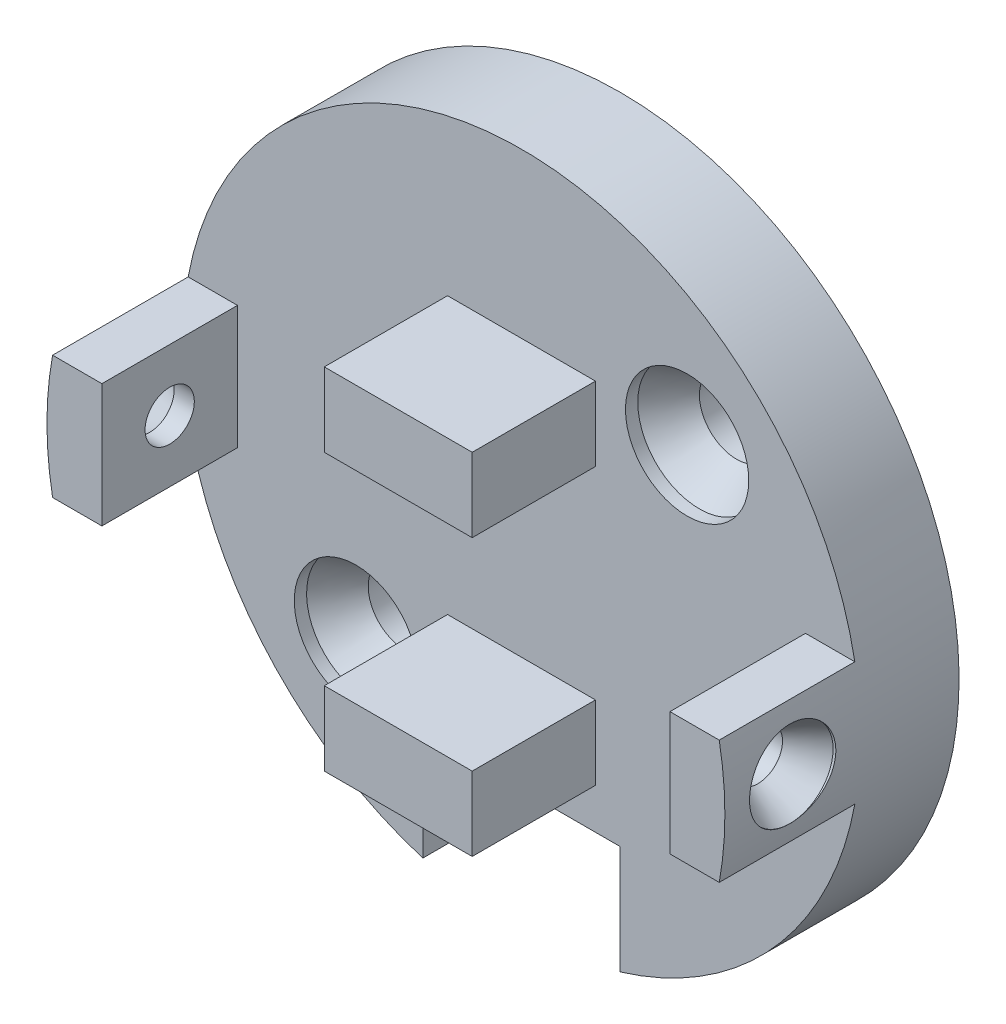
SolidWorks part; units mm, degrees
ref_plane "Front Plane" through (0, 0, 0) normal (0, 0, 1) x (1, 0, 0)
ref_plane "Top Plane" through (0, 0, 0) normal (0, 1, 0) x (1, 0, 0)
ref_plane "Right Plane" through (0, 0, 0) normal (1, 0, 0) x (0, 0, -1)
sketch "Sketch1" plane through (0, 0, 0) normal (0, 0, 1) x (1, 0, 0)
  circle A0 centre (0, 0) radius 13.75
  dimension "D1" = 27.5
extrude "Boss-Extrude1" add sketch "Sketch1" along normal blind 4
sketch "Sketch2" plane through (0, 0, 4) normal (0, 0, 1) x (1, 0, 0)
  line L0 (0, 0) -> (0, 13.75) construction
  line L1 (-13.75, 0) -> (13.75, 0) construction
  line L2 (-13.5208, 2.5) -> (-11.5208, 2.5)
  line L3 (-11.5208, 2.5) -> (-11.5208, -2.5)
  line L4 (-11.5208, -2.5) -> (-13.5208, -2.5)
  line L8 (13.5208, -2.5) -> (11.5208, -2.5)
  line L9 (11.5208, -2.5) -> (11.5208, 2.5)
  line L10 (11.5208, 2.5) -> (13.5208, 2.5)
  line L11 (2.5, 13.5208) -> (2.5, 11.5208) [skipped]
  line L12 (2.5, 11.5208) -> (-2.5, 11.5208) [skipped]
  line L13 (-2.5, 11.5208) -> (-2.5, 13.5208) [skipped]
  circle A0 centre (0, 0) radius 13.75 construction
  circle A1 centre (0, 0) radius 13.75
  point P11 (-11.5208, 0)
  point P14 (11.5208, 0)
  point P21 (0, 0)
  circle M12 centre (0, 0) radius 13.75
  dimension "D1" = 0
  dimension "D2" = 5
  dimension "D3" = 2
  dimension "D5" = 2
  dimension "D6" = 5
  dimension "D4" = 3
extrude "Boss-Extrude2" add sketch "Sketch2" along normal blind 5.5 contours L4 L3 L2 M12 | L10 L9 L8 M12 region at (-12.5984, 0, 4) region at (12.5984, 0, 4)
ref_plane "Plane1" through (0, 0, 6.75) normal (0, 0, 1) x (1, 0, 0)
sketch "Sketch6" plane through (0, 0, 6.75) normal (0, 0, 1) x (1, 0, 0)
  line L0 (-13.6382, 1.75) -> (-13.6382, -1.75)
  line L1 (-11.5208, 0) -> (-13.6382, 0) construction
  line L2 (-13.6382, 1.75) -> (-12.3382, 1)
  line L9 (-12.3382, 1) -> (-11.5208, 1)
  line L10 (-11.5208, 1) -> (-11.5208, 0)
  line L11 (-13.6382, 1.75) -> (-15.1747, 1.75)
  line L12 (-15.1747, 1.75) -> (-15.1747, 0)
  line L13 (-15.1747, 0) -> (-11.5208, 0)
  line L14 (-13.5208, -2.5) -> (-11.5208, -2.5)
  line L15 (-13.5208, -2.5) -> (-11.5208, -2.5)
  line L16 (-11.5208, -2.5) -> (-11.5208, 2.5)
  line L17 (-11.5208, -2.5) -> (-11.5208, 2.5)
  line L18 (-11.5208, 2.5) -> (-13.5208, 2.5)
  line L19 (-11.5208, 2.5) -> (-13.5208, 2.5)
  arc A1 (-13.5208, 2.5) -> (-13.5208, -2.5) centre (0, 0) ccw
  arc A2 (-13.5208, 2.5) -> (-13.5208, -2.5) centre (0, 0) ccw
  point P4 (-13.75, 0)
  dimension "D2" = 3.5
  dimension "D3" = 1
  dimension "D4" = 1.3
  dimension "D1" = 0
revolve "Cut-Revolve2" cut sketch "Sketch6" angle 360 about L1 region at (-12.6965, 0.6404, 6.75) region at (-14.4434, 0.8861, 6.75) region at (-13.6829, 0.6566, 6.75)
sketch "Sketch7" plane through (0, 0, 0) normal (0, 1, 0) x (1, 0, 0)
  line L0 (0, 0) -> (0, -11.7876) construction
pattern_circular "CirPattern1" count 2 over 180 about axis through (0, 0, 0) along (0, 0, 1) of "Cut-Revolve2" reverse direction yes
sketch "Sketch9" plane through (0, 0, 0) normal (0, 0, -1) x (-1, 0, 0)
  line L0 (0, 0) -> (0, 13.75) construction
  line L1 (-6.7175, 6.7175) -> (6.7175, -6.7175) construction
  circle A0 centre (0, 0) radius 13.75 construction
  circle A1 centre (0, 0) radius 13.75
  circle A2 centre (-6.7175, 6.7175) radius 1.6
  circle A3 centre (6.7175, -6.7175) radius 1.6
  point P7 (0, 0)
  dimension "D3" = 3.2
  dimension "D1" = 45
  dimension "D2" = 19
ref_plane "Plane2" through (0, 0, 0) normal (-0.7071, 0.7071, 0) x (-0.7071, -0.7071, 0)
sketch "Sketch10" plane through (0, 0, 0) normal (-0.7071, 0.7071, 0) x (-0.7071, -0.7071, 0)
  line L0 (-9.5, 0) -> (-9.5, 3.5)
  line L1 (-11.1, 0) -> (-7.9, 0) construction
  line L2 (-9.5, 0) -> (-8, 0)
  line L3 (-13.75, 0) -> (13.75, 0) construction
  line L4 (-8, 0) -> (-8, 2)
  line L5 (-8, 2) -> (-7, 3.5)
  line L6 (-7, 3.5) -> (-9.5, 3.5) construction
  line L7 (-7, 3.5) -> (-7, 4.0498)
  line L9 (-7, 4.0498) -> (-9.5, 4.0498)
  line L10 (-9.5, 4.0498) -> (-9.5, 3.5)
  point P0 (-9.5, 0)
  dimension "D1" = 1.5
  dimension "D2" = 2
  dimension "D3" = 1.5
  dimension "D4" = 2.5
revolve "Cut-Revolve3" cut sketch "Sketch10" angle 360 about L0 region at (6.0914, 6.0914, 1.9062) region at (5.8336, 5.8336, 3.7749)
ref_plane "Plane3" through (0, 0, 0) normal (-0.7071, -0.7071, 0) x (0, 0, 1)
mirror "Mirror1" about plane through (0, 0, 0) normal (-0.7071, -0.7071, 0) of "Cut-Revolve3"
sketch "Sketch11" plane through (0, 0, 4) normal (0, 0, 1) x (1, 0, 0)
  line L0 (-4, -13.75) -> (4, -13.75)
  line L1 (-4, -13.75) -> (4, -13.75)
  line L2 (-4, -13.75) -> (-4, -8.75)
  line L3 (4, -13.75) -> (4, -8.75)
  line L4 (-4, -8.75) -> (4, -8.75)
  circle A0 centre (0, 0) radius 13.75 construction
  circle A1 centre (0, 0) radius 13.75
  point P6 (0, -13.75)
  arc M14 (-13.5208, -2.5) -> (13.5208, -2.5) centre (0, 0) ccw
  dimension "D1" = 8
  dimension "D2" = 5
extrude "Cut-Extrude3" cut sketch "Sketch11" against normal through all contours L4 L2 L3 M14 region at (0, -11.155, 4)
sketch "Sketch12" plane through (0, 0, 4) normal (0, 0, 1) x (1, 0, 0)
  line L0 (-3, 4.1) -> (3, 4.1)
  line L1 (-3, -7.1) -> (3, -7.1)
  line L2 (-3, -7.1) -> (-3, 7.1)
  line L3 (-3, 7.1) -> (3, 7.1)
  line L4 (3, -7.1) -> (3, 7.1)
  line L5 (0, 7.1) -> (0, -7.1) construction
  line L6 (-3, 0) -> (3, 0) construction
  line L7 (-3, -4.1) -> (3, -4.1)
  line L8 (0, -4.1) -> (0, 4.1)
  point P0 (0, 0)
  point P11 (0, 0)
  dimension "D1" = 6
  dimension "D2" = 8.2
  dimension "D3" = 14.2
extrude "Boss-Extrude4" add sketch "Sketch12" along normal blind 5 contours L0 L4 L3 L2 | L7 L2 L1 L4 region at (0, 5.6, 4) region at (0, -5.6, 4)
